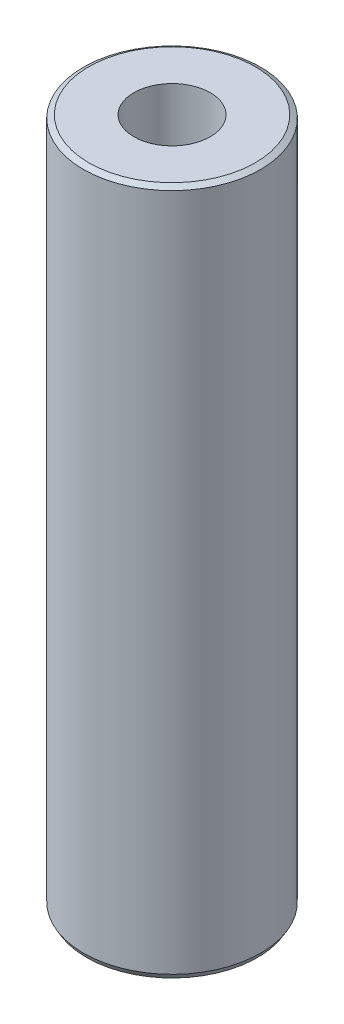
SolidWorks part; units mm, degrees
ref_plane "Front Plane" through (0, 0, 0) normal (0, 0, 1) x (1, 0, 0)
ref_plane "Top Plane" through (0, 0, 0) normal (0, 1, 0) x (1, 0, 0)
ref_plane "Right Plane" through (0, 0, 0) normal (1, 0, 0) x (0, 0, -1)
sketch "Sketch1" plane through (0, 0, 0) normal (0, 1, 0) x (1, 0, 0)
  circle A0 centre (0, 0) radius 57.5
  dimension "SHAFT_OD" = 115
extrude "Boss-Extrude1" add sketch "Sketch1" along normal blind 445.8523
sketch "Sketch2" plane through (0, 0, 0) normal (0, 1, 0) x (1, 0, 0)
  circle A0 centre (0, 0) radius 24.7828
  dimension "BORE_D" = 49.5656
extrude "Cut-Extrude1" cut sketch "Sketch2" along normal through all
chamfer "Chamfer1" distance 2.0102 angle 60 2 edges at (0, 445.8523, 57.5) (0, 0, 57.5) first distance on face at (0, 445.8523, 57.5) first distance on face at (0, 0, 24.7828)
